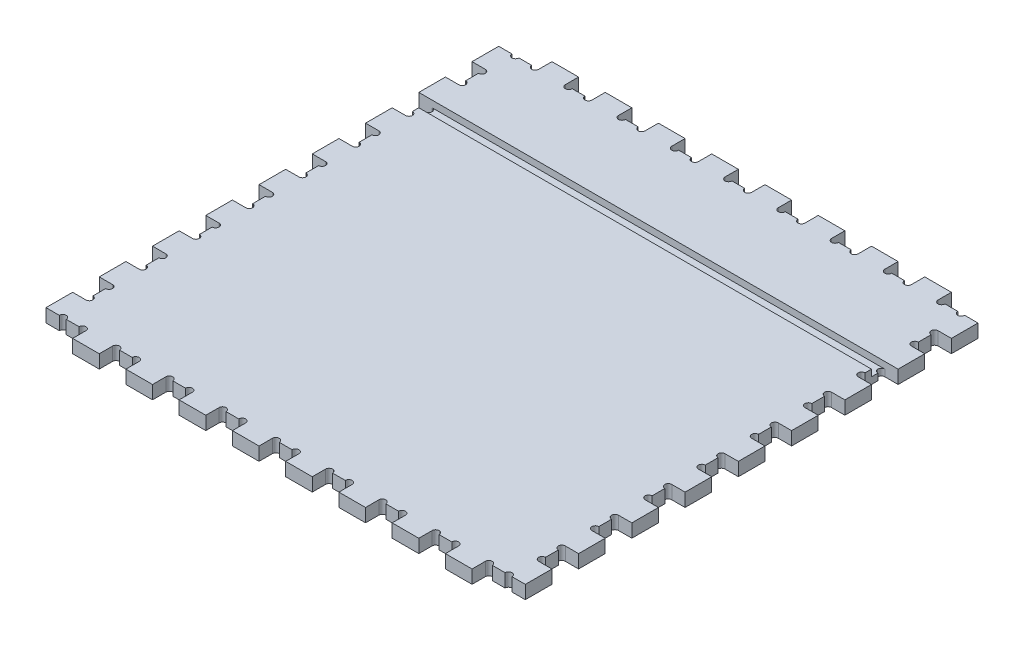
SolidWorks part; units mm, degrees
ref_plane "Front Plane" through (0, 0, 0) normal (0, 0, 1) x (1, 0, 0)
ref_plane "Top Plane" through (0, 0, 0) normal (0, 1, 0) x (1, 0, 0)
ref_plane "Right Plane" through (0, 0, 0) normal (1, 0, 0) x (0, 0, -1)
sketch "Sketch1" plane through (0, 0, 0) normal (0, 1, 0) x (1, 0, 0)
  line L1 (228.6, -228.6) -> (-228.6, -228.6)
  line L2 (228.6, -228.6) -> (228.6, 228.6)
  line L3 (228.6, 228.6) -> (-228.6, 228.6)
  line L4 (-228.6, -228.6) -> (-228.6, 228.6)
  line L5 (228.6, -228.6) -> (-228.6, 228.6) construction
  line L6 (228.6, 228.6) -> (-228.6, -228.6) construction
  point P0 (0, 0)
  dimension "D1" = 457.2
  dimension "D2" = 457.2
extrude "Boss-Extrude1" add sketch "Sketch1" along normal blind 12.7
sketch "Sketch2" plane through (0, 12.7, 0) normal (0, 1, 0) x (1, 0, 0)
  line L0 (228.6, 228.6) -> (-228.6, 228.6) construction
  line L1 (-215.9, 228.6) -> (-190.5, 228.6)
  line L2 (-215.9, 228.6) -> (-215.9, 215.9)
  line L3 (-215.9, 215.9) -> (-190.5, 215.9)
  line L4 (-190.5, 228.6) -> (-190.5, 215.9)
  line L5 (-215.9, 215.9) -> (-228.6, 215.9) construction
  line L6 (-228.6, 228.6) -> (-228.6, -228.6) construction
  circle A0 centre (-212.598, 215.9) radius 3.302
  circle A1 centre (-193.802, 215.9) radius 3.302
  line M8 (228.6, 228.6) -> (-228.6, 228.6)
  dimension "D3" = 6.604
  dimension "D4" = 6.604
  dimension "D1" = 25.4
  dimension "D2" = 12.7
  dimension "D5" = 12.7
extrude "Cut-Extrude1" cut sketch "Sketch2" against normal blind 12.7 contours A1 L4 L2 A0 L3 M8 | L3 A0 | L3 A1 | L3 A1 | L3 A0 region at (-203.2, 12.7, -222.8379) region at (-212.598, 12.7, -217.3014) region at (-212.598, 12.7, -214.4986) region at (-193.802, 12.7, -214.4986) region at (-193.802, 12.7, -217.3014)
pattern_linear "LPattern1" count 9 spacing 50.8 along (1, 0, 0) of "Cut-Extrude1"
ref_plane "Plane1" through (0, 0, 0) normal (0, 0, -1) x (-1, 0, 0)
ref_plane "Plane2" through (0, 0, 0) normal (-1, 0, 0) x (0, 0, 1)
mirror "Mirror1" about plane through (0, 0, 0) normal (0, 0, -1) of "LPattern1"
sketch "Sketch3" plane through (0, 12.7, 0) normal (0, 1, 0) x (1, 0, 0)
  line L1 (-228.6, 228.6) -> (-215.9, 228.6)
  line L2 (-228.6, 228.6) -> (-228.6, 215.9)
  line L3 (-228.6, 215.9) -> (-215.9, 215.9)
  line L4 (-215.9, 228.6) -> (-215.9, 215.9)
extrude "Cut-Extrude2" cut sketch "Sketch3" against normal through all
mirror "Mirror2" about plane through (0, 0, 0) normal (-1, 0, 0) of "Cut-Extrude2"
mirror "Mirror3" about plane through (0, 0, 0) normal (0, 0, -1) of "Mirror2"
sketch "Sketch4" plane through (0, 12.7, 0) normal (0, 1, 0) x (1, 0, 0)
  line L0 (-228.6, 215.9) -> (-228.6, -215.9) construction
  line L1 (-228.6, 190.5) -> (-215.9, 190.5)
  line L2 (-228.6, 190.5) -> (-228.6, 165.1)
  line L3 (-228.6, 165.1) -> (-215.9, 165.1)
  line L4 (-215.9, 190.5) -> (-215.9, 165.1)
  line L5 (-215.9, 190.5) -> (-186.3664, 190.5) construction
  line L6 (-186.3664, 190.5) -> (-186.3664, 228.6) construction
  line L7 (-165.1, 228.6) -> (-190.5, 228.6) construction
  circle A0 centre (-215.9, 187.198) radius 3.302
  circle A1 centre (-215.9, 168.402) radius 3.302
  dimension "D3" = 6.604
  dimension "D4" = 6.604
  dimension "D1" = 12.7
  dimension "D2" = 25.4
  dimension "D5" = 38.1
extrude "Cut-Extrude3" cut sketch "Sketch4" against normal through all contours A1 L4 A0 L1 L2 L3 | L4 A0 | L4 A1 | L4 A1 | L4 A0 region at (-222.8379, 12.7, -177.8) region at (-214.4986, 12.7, -187.198) region at (-217.3014, 12.7, -187.198) region at (-217.3014, 12.7, -168.402) region at (-214.4986, 12.7, -168.402)
pattern_linear "LPattern2" count 9 spacing 50.8 along (0, 0, 1) of "Cut-Extrude3"
mirror "Mirror4" about plane through (0, 0, 0) normal (-1, 0, 0) of "LPattern2"
sketch "Sketch5" plane through (0, 12.7, 0) normal (0, 1, 0) x (1, 0, 0)
  line L1 (-165.1, 139.7) -> (-139.7, 139.7)
  line L2 (-165.1, 139.7) -> (-165.1, 127)
  line L3 (-165.1, 127) -> (-139.7, 127)
  line L4 (-139.7, 139.7) -> (-139.7, 127)
  line L6 (-165.1, 215.9) -> (-165.1, 139.7) construction
  circle A0 centre (-161.798, 139.7) radius 3.302
  circle A1 centre (-143.002, 139.7) radius 3.302
  circle A2 centre (-161.798, 127) radius 3.302
  circle A3 centre (-143.002, 127) radius 3.302
  dimension "D3" = 6.604
  dimension "D1" = 12.7
  dimension "D2" = 25.4
  dimension "D4" = 76.2
extrude "Cut-Extrude4" [suppressed] cut sketch "Sketch5" against normal through all contours A3 L4 A1 L1 A0 L2 A2 L3 | L1 A0 | L1 A0 | L3 A2 | L3 A2 | L3 A3 | L3 A3 | A1
pattern_linear "LPattern3" [suppressed] count 7 spacing 50.8 of bodies 111
sketch "Sketch7" plane through (0, 12.7, 0) normal (0, 1, 0) x (1, 0, 0)
  line L0 (215.9, 133.096) -> (215.9, 120.904) construction
  line L1 (-215.9, 139.7) -> (215.9, 139.7)
  line L2 (-215.9, 139.7) -> (-215.9, 127)
  line L3 (-215.9, 127) -> (215.9, 127)
  line L4 (215.9, 139.7) -> (215.9, 127)
  dimension "D1" = 12.7
extrude "Cut-Extrude5" cut sketch "Sketch7" against normal blind 6.35
